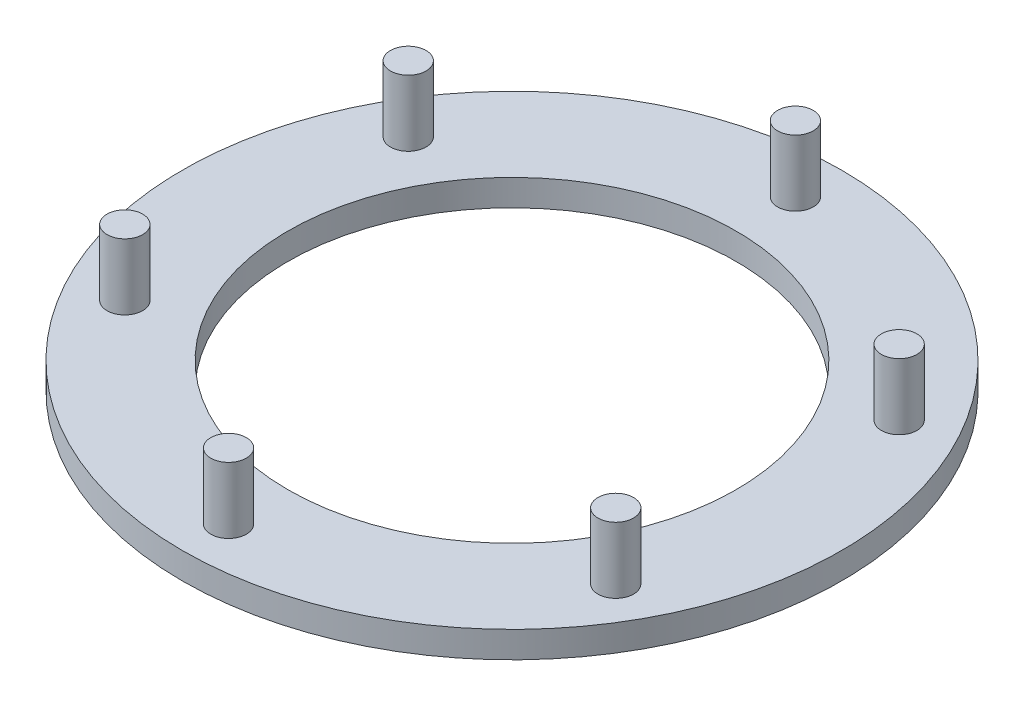
SolidWorks part; units mm, degrees
ref_plane "Front Plane" through (0, 0, 0) normal (0, 0, 1) x (1, 0, 0)
ref_plane "Top Plane" through (0, 0, 0) normal (0, 1, 0) x (1, 0, 0)
ref_plane "Right Plane" through (0, 0, 0) normal (1, 0, 0) x (0, 0, -1)
sketch "Sketch1" plane through (0, 0, 0) normal (0, 1, 0) x (1, 0, 0)
  line L0 (0, 0) -> (0, 17) construction
  circle A0 centre (0, 0) radius 25
  circle A1 centre (0, 0) radius 21.5 construction
  circle A2 centre (0, 21.5) radius 1.35
  circle A3 centre (18.6195, 10.75) radius 1.35
  circle A4 centre (18.6195, -10.75) radius 1.35
  circle A5 centre (0, -21.5) radius 1.35
  circle A6 centre (-18.6195, -10.75) radius 1.35
  circle A7 centre (-18.6195, 10.75) radius 1.35
  circle A11 centre (0, 0) radius 17
  point P19 (0, 0)
  dimension "D1" = 50
  dimension "D2" = 43
  dimension "D3" = 2.7
  dimension "D6" = 17
extrude "Boss-Extrude1" add sketch "Sketch1" along normal blind 2
extrude "Boss-Extrude2" add sketch "Sketch1<3>" along normal blind 7 contours A6 | A7 | A2 | A3 | A4 | A5 region at (0, 0, -21.5) region at (18.6195, 0, -10.75) region at (18.6195, 0, 10.75) region at (0, 0, 21.5) region at (-18.6195, 0, 10.75) region at (-18.6195, 0, -10.75)
sketch "Sketch1<3>" plane through (0, 0, 0) normal (0, 1, 0) x (1, 0, 0) same geometry as "Sketch1"
